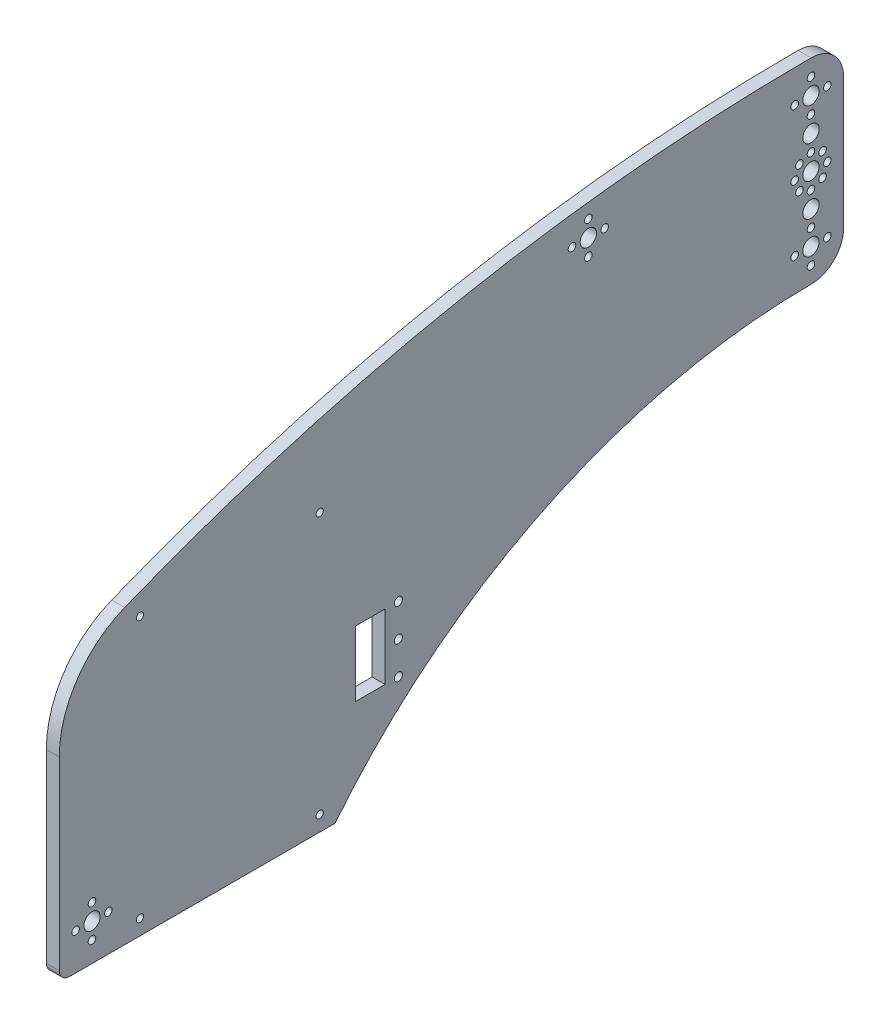
SolidWorks part; units mm, degrees
ref_plane "Front Plane" through (0, 0, 0) normal (0, 0, 1) x (1, 0, 0)
ref_plane "Top Plane" through (0, 0, 0) normal (0, 1, 0) x (1, 0, 0)
ref_plane "Right Plane" through (0, 0, 0) normal (1, 0, 0) x (0, 0, -1)
sketch "Sketch1" plane through (0, 0, 0) normal (1, 0, 0) x (0, 0, -1)
  line L0 (352, 110) -> (352, 126) construction
  line L1 (352, 110) -> (352, 118) construction
  line L2 (335.394, 142) -> (383.5261, 142) construction
  line L3 (352, 174) -> (352, 166) construction
  line L4 (352, 174) -> (352, 158) construction
  line L5 (-16, -18) -> (16, -18) construction
  line L6 (16, -18) -> (16, -50) construction
  line L7 (16, -50) -> (-16, -50) construction
  line L8 (-16, 77.6494) -> (-16, -13)
  line L9 (-11, -18) -> (119, -18)
  line L10 (368, 174) -> (368, 110)
  line L11 (23.5, 117.5) -> (23.5, -10.5) construction
  line L12 (16, 125) -> (119, 125) construction
  line L13 (16, 125) -> (16, -18) construction
  line L14 (16, -18) -> (119, -18) construction
  line L15 (119, 125) -> (119, -18) construction
  line L16 (23.5, -10.5) -> (111.5, -10.5) construction
  line L17 (111.5, 117.5) -> (111.5, -10.5) construction
  line L18 (23.5, 117.5) -> (111.5, 117.5) construction
  line L19 (129, 28.6253) -> (143.5, 28.6253)
  line L20 (129, 28.6253) -> (129, 60.6253)
  line L21 (143.5, 28.6253) -> (143.5, 60.6253)
  line L22 (129, 60.6253) -> (143.5, 60.6253)
  line L23 (150, 28.6253) -> (150, 60.6253) construction
  circle A0 centre (352, 110) radius 4
  circle A1 centre (352, 118) radius 1.85
  circle A2 centre (352, 126) radius 4
  circle A3 centre (352, 134) radius 1.85
  circle A4 centre (352, 142) radius 4
  circle A6 centre (352, 150) radius 1.85 [skipped]
  circle A7 centre (360, 110) radius 1.85
  circle A8 centre (352, 102) radius 1.85
  circle A9 centre (344, 110) radius 1.85
  circle A10 centre (346.3431, 136.3431) radius 1.85
  circle A11 centre (344, 142) radius 1.85
  circle A12 centre (346.3431, 147.6569) radius 1.85
  circle A13 centre (352, 150) radius 1.85
  circle A14 centre (357.6569, 147.6569) radius 1.85
  circle A15 centre (360, 142) radius 1.85
  circle A16 centre (357.6569, 136.3431) radius 1.85
  circle A17 centre (344, 174) radius 1.85
  circle A18 centre (352, 182) radius 1.85
  circle A19 centre (360, 174) radius 1.85
  circle A20 centre (352, 158) radius 4
  circle A21 centre (352, 166) radius 1.85
  circle A22 centre (352, 174) radius 4
  arc A23 (16, 125) -> (352, 190) centre (352, -710.9308) cw
  arc A24 (-16, -13) -> (-11, -18) centre (-11, -13) ccw
  arc A25 (352, 94) -> (119, -18) centre (352, -204.3616) ccw
  arc A26 (352, 190) -> (368, 174) centre (352, 174) cw
  arc A27 (368, 110) -> (352, 94) centre (352, 110) cw
  circle A28 centre (0, 0) radius 4
  circle A29 centre (8, 0) radius 1.85
  circle A30 centre (0, -8) radius 1.85
  circle A31 centre (-8, 0) radius 1.85
  circle A32 centre (0, 8) radius 1.85
  circle A33 centre (23.5, 117.5) radius 1.75
  circle A34 centre (111.5, 117.5) radius 1.75
  circle A35 centre (111.5, -10.5) radius 1.75
  circle A36 centre (23.5, -10.5) radius 1.75
  arc A37 (16, 125) -> (-16, 77.6494) centre (35.0324, 77.6494) ccw
  circle A38 centre (150, 28.6253) radius 2
  circle A39 centre (150, 44.6253) radius 2
  circle A40 centre (150, 60.6253) radius 2
  circle A41 centre (243, 168.2691) radius 4
  circle A42 centre (251, 168.2691) radius 1.85
  circle A43 centre (243, 160.2691) radius 1.85
  circle A44 centre (235, 168.2691) radius 1.85
  circle A45 centre (243, 176.2691) radius 1.85
  point P25 (352, 142)
  point P38 (352, 142)
  point P70 (0, -50)
  point P79 (0, 0)
  point P113 (243, 168.2691)
  dimension "D1" = 8
  dimension "D2" = 3.7
  dimension "D12" = 5
  dimension "D18" = 8
  dimension "D19" = 3.7
  dimension "D22" = 3.5
  dimension "D14" = 16
  dimension "D25" = 4
  dimension "D28" = 10
  dimension "D29" = 10
  dimension "D30" = 8
  dimension "D31" = 3.7
  dimension "D3" = 8
  dimension "D5" = 16
  dimension "D7" = 8
  dimension "D8" = 32
  dimension "D9" = 336
  dimension "D10" = 160
  dimension "D11" = 16
  dimension "D13" = 16
  dimension "D15" = 16
  dimension "D16" = 18
  dimension "D17" = 8
  dimension "D23" = 143
  dimension "D24" = 103
  dimension "D26" = 6.5
  dimension "D27" = 14.5
  dimension "D32" = 8
  dimension "D34" = 15
  dimension "D35" = 125
  dimension "D21" = 7.5
  dimension "D4" = 3
  dimension "D6" = 4
  dimension "D20" = 4
  dimension "D33" = 4
extrude "Boss-Extrude2" add sketch "Sketch1" along normal blind 6.35
